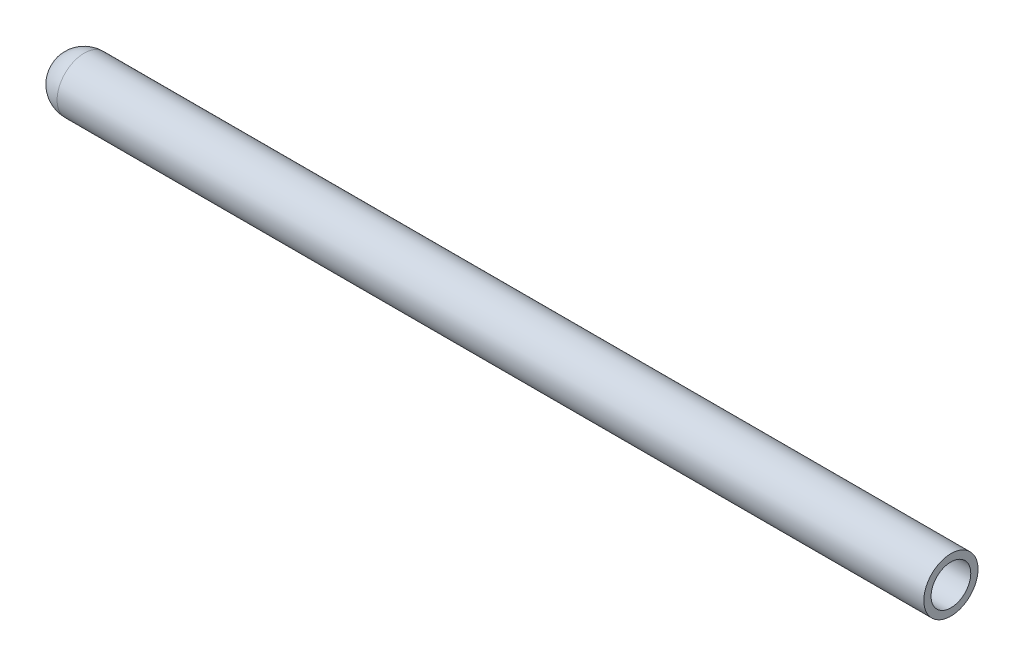
SolidWorks part; units mm, degrees
material "S-Glass Fiber"
ref_plane "Front Plane" through (0, 0, 0) normal (0, 0, 1) x (1, 0, 0)
ref_plane "Top Plane" through (0, 0, 0) normal (0, 1, 0) x (1, 0, 0)
ref_plane "Right Plane" through (0, 0, 0) normal (1, 0, 0) x (0, 0, -1)
sketch "Sketch1" plane through (0, 0, 0) normal (1, 0, 0) x (0, 0, -1)
  circle A0 centre (0, 0) radius 9.525
  dimension "D1" = 19.05
extrude "Boss-Extrude1" add sketch "Sketch1" against normal blind 304.8
dome "Dome1" faces to dome 1 distance 9.525 reverse direction no elliptical dome no face at (-304.8, 0, -9.525) parameters "D1"=9.525
shell "Shell1" thickness 2.54 removed face at (0, 0, -9.525)
